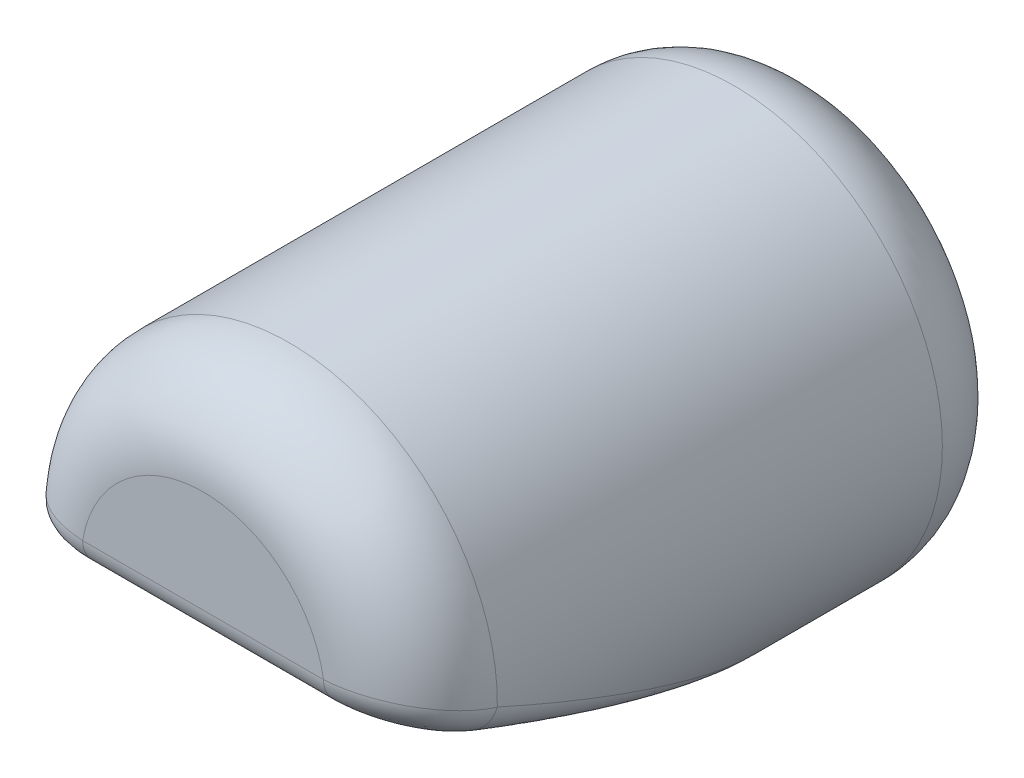
SolidWorks part; units mm, degrees
ref_plane "Front Plane" through (0, 0, 0) normal (0, 0, 1) x (1, 0, 0)
ref_plane "Top Plane" through (0, 0, 0) normal (0, 1, 0) x (1, 0, 0)
ref_plane "Right Plane" through (0, 0, 0) normal (1, 0, 0) x (0, 0, -1)
sketch "Sketch2" plane through (0, 0, 0) normal (0, 0, 1) x (1, 0, 0)
  circle A0 centre (0, 0) radius 7.25
  dimension "D1" = 14.5
extrude "Boss-Extrude1" add sketch "Sketch2" along normal blind 21.5
ref_point "Point1"
ref_point "Point2"
fillet "Fillet1" radius 3 2 edges at (7.25, 0, 21.5) (7.25, 0, 0)
sketch "Sketch3" plane through (0, 0, 0) normal (1, 0, 0) x (0, 0, -1)
  line L0 (-21.5, 0) -> (-3, -7.25)
  line L1 (-3, -7.25) -> (-3, -10.4048)
  line L2 (-3, -10.4048) -> (-21.5, -10.4048)
  line L3 (-21.5, 0) -> (-21.5, 1000) construction
  line L4 (-21.5, 50) -> (-21.5, -50) construction
  line L5 (-21.5, -10.4048) -> (-21.5, 0)
extrude "Cut-Extrude1" cut sketch "Sketch3" against normal blind 10 and the other way blind 10
fillet "Fillet2" radius 1 5 edges at (4.6925, -5.5266, 7.3977) (6.5656, -0.4351, 20.3898) (-4.6925, -5.5266, 7.3977) (-6.5847, -0.4447, 20.3652) (0, 0, 21.5)
